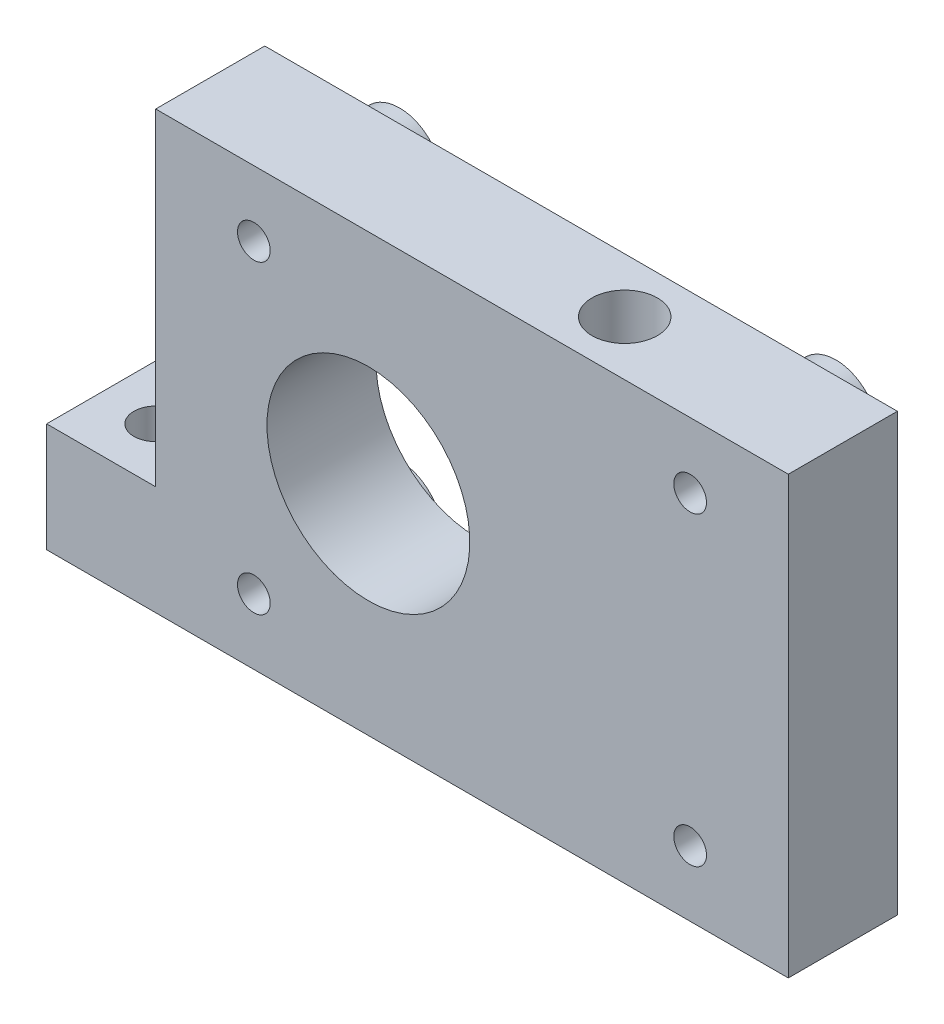
SolidWorks part; units mm, degrees
ref_plane "Front Plane" through (0, 0, 0) normal (0, 0, 1) x (1, 0, 0)
ref_plane "Top Plane" through (0, 0, 0) normal (0, 1, 0) x (1, 0, 0)
ref_plane "Right Plane" through (0, 0, 0) normal (1, 0, 0) x (0, 0, -1)
sketch "Sketch1" plane through (0, 0, 0) normal (0, 0, 1) x (1, 0, 0)
  circle A0 centre (-49, 7.836) radius 1.5
  circle A1 centre (-49, 7.836) radius 3.9
  circle A2 centre (-49, 35.836) radius 1.5
  circle A3 centre (-49, 35.836) radius 3.9
  circle A4 centre (-9, 35.836) radius 1.5
  circle A5 centre (-9, 35.836) radius 3.9
  circle A6 centre (-9, 7.836) radius 1.5
  circle A7 centre (-9, 7.836) radius 3.9
extrude "Boss-Extrude1" add sketch "Sketch1" along normal up to surface (13.3616 mm away)
sketch "Sketch2" plane through (0, 0, -1.8) normal (0, 0, 1) x (1, 0, 0)
  line L0 (-58, 1.836) -> (0, 1.836) construction
  line L1 (-58, 41.836) -> (0, 41.836)
  line L2 (-58, 41.836) -> (-58, 1.836)
  line L3 (-58, 1.836) -> (0, 1.836)
  line L4 (0, 41.836) -> (0, 1.836)
  line L5 (-58, 41.836) -> (0, 1.836) construction
  line L6 (-58, 1.836) -> (0, 41.836) construction
  point P4 (-29, 21.836)
  circle M1 centre (-9, 7.836) radius 3.9
  circle M2 centre (-9, 35.836) radius 3.9
  circle M3 centre (-49, 35.836) radius 3.9
  circle M4 centre (-49, 7.836) radius 3.9
  circle M5 centre (-38.5, 21.836) radius 9.3
  line M6 (0, 1.836) -> (0, 5.29)
  line M7 (0, 5.29) -> (0, 38.4413)
  line M8 (0, 38.4413) -> (0, 41.836)
  line M9 (0, 41.836) -> (-58, 41.836)
  line M10 (-58, 41.836) -> (-58, 1.836)
  line M11 (-58, 1.836) -> (0, 1.836)
extrude "Boss-Extrude2" add sketch "Sketch2" against normal blind 10 from surface contours M11 M6 M7 M8 M9 M10 M2 M4 M5 M3 M1 region at (-27.6101, 21.836, -1.8) starting at face at (-49, 37.336, 13.3616)
sketch "Sketch4" plane through (0, 41.836, 0) normal (0, 1, 0) x (1, 0, 0)
  line L0 (0, -8.3616) -> (-58, -8.3616) construction
  line L1 (0, -3.3616) -> (0, -13.3616) construction
  line L2 (-58, -3.3616) -> (-58, -13.3616) construction
  circle A0 centre (-20, -8.3616) radius 3
  circle A1 centre (-20, -8.3616) radius 2
  dimension "D1" = 6
  dimension "D2" = 4
  dimension "D3" = 20
extrude "Cut-Extrude1" cut sketch "Sketch4" against normal blind 25 contours L0 A0 A1 | A1 L0 | A0 L0 A1 | L0 A1 region at (-20, 41.836, 11.2945) region at (-17.5, 41.836, 8.2945) region at (-20, 41.836, 9.2104) region at (-20, 41.836, 7.5127)
extrude "Cut-Extrude2" cut sketch "Sketch4<3>" against normal through all contours L0 A1 | A1 L0 region at (-20, 41.836, 9.2104) region at (-20, 41.836, 7.5127)
sketch "Sketch4<3>" plane through (0, 41.836, 0) normal (0, 1, 0) x (1, 0, 0) same geometry as "Sketch4"
sketch "Sketch5" plane through (0, 1.836, 0) normal (0, 1, 0) x (1, 0, 0)
  line L0 (271.6524, -13.3616) -> (-80.3476, -13.3616) construction
  line L1 (-58, -3.3616) -> (-68, -3.3616)
  line L2 (-58, -3.3616) -> (-58, -13.3616)
  line L3 (-58, -13.3616) -> (-68, -13.3616)
  line L4 (-68, -3.3616) -> (-68, -13.3616)
  line L5 (-58, -3.3616) -> (-68, -13.3616) construction
  line L6 (-58, -13.3616) -> (-68, -3.3616) construction
  circle A0 centre (-63, -8.3616) radius 2
  point P4 (-63, -8.3616)
  dimension "D2" = 4
  dimension "D1" = 10
extrude "Boss-Extrude3" add sketch "Sketch5" along normal blind 10
